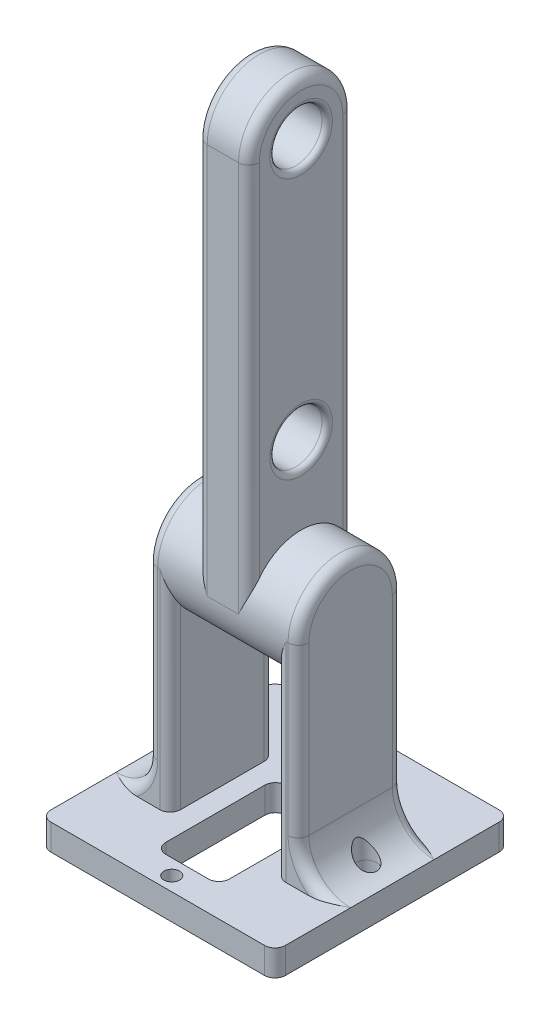
SolidWorks part; units mm, degrees
other "Base"
other "Brazo"
ref_plane "Alzado" through (0, 0, 0) normal (0, 0, 1) x (1, 0, 0)
ref_plane "Planta" through (0, 0, 0) normal (0, 1, 0) x (1, 0, 0)
ref_plane "Vista lateral" through (0, 0, 0) normal (1, 0, 0) x (0, 0, -1)
sketch "Croquis1" plane through (0, 0, 0) normal (0, 1, 0) x (1, 0, 0)
  line L0 (-17.5, 5.35) -> (17.5, 5.35) construction
  line L1 (-6.1, -11.5) -> (6.1, -11.5)
  line L2 (-6.1, -11.5) -> (-6.1, 11.5)
  line L3 (-6.1, 11.5) -> (6.1, 11.5)
  line L4 (6.1, -11.5) -> (6.1, 11.5)
  line L5 (-6.1, -11.5) -> (6.1, 11.5) construction
  line L6 (-6.1, 11.5) -> (6.1, -11.5) construction
  line L11 (0, 14.45) -> (0, -14.45) construction
  line L13 (-17.5, 7.35) -> (-6.1, 7.35) construction
  line L18 (-6.1, 11.5) -> (6.1, 11.5) construction
  line L22 (-22.5, -17.15) -> (22.5, -17.15)
  line L23 (-22.5, -17.15) -> (-22.5, 27.85)
  line L24 (-22.5, 27.85) -> (22.5, 27.85)
  line L25 (22.5, -17.15) -> (22.5, 27.85)
  line L26 (-22.5, -17.15) -> (22.5, 27.85) construction
  line L27 (-22.5, 27.85) -> (22.5, -17.15) construction
  line L30 (-6.1, -11.5) -> (6.1, -11.5) construction
  circle A0 centre (-17.5, 5.35) radius 2
  circle A1 centre (17.5, 5.35) radius 2
  circle A12 centre (0, 14.45) radius 1.5
  circle A13 centre (0, -14.45) radius 1.5
  point P0 (0, 0)
  point P14 (0, 5.35)
  point P17 (0, 0)
  point P41 (0, 5.35)
  dimension "D4" = 4
  dimension "D5" = 45
  dimension "D6" = 45
  dimension "D7" = 4
  dimension "D12" = 3
  dimension "D13" = 3
  dimension "D1" = 12.2
  dimension "D2" = 23
  dimension "D3" = 9.1
  dimension "D8" = 35
  dimension "D9" = 28.9
extrude "Saliente-Extruir1" add sketch "Croquis1" against normal blind 5 contours L25 L24 L23 A1 A0 L4 L1 L2 L3 region at (-21.8636, 0, -5.35)
sketch "Croquis2" plane through (0, -5, 0) normal (0, -1, 0) x (1, 0, 0)
  line L4 (-22.5, -27.85) -> (22.5, -27.85)
  line L5 (22.5, 17.15) -> (-22.5, 17.15)
  line L6 (22.5, 17.15) -> (-22.5, 17.15)
  line L7 (-22.5, 17.15) -> (-22.5, -27.85)
  line L8 (-22.5, -27.85) -> (22.5, -27.85)
  line L12 (-22.5, 17.15) -> (-22.5, -27.85)
  line L13 (22.5, -27.85) -> (22.5, 17.15)
  line L14 (22.5, -27.85) -> (22.5, 17.15)
  circle A0 centre (0, -14.45) radius 1.5 construction
  circle A1 centre (0, -14.45) radius 1.5
  circle A2 centre (0, 14.45) radius 1.5 construction
  circle A3 centre (0, 14.45) radius 1.5
  circle A12 centre (0, 14.45) radius 2
  circle A13 centre (0, -14.45) radius 2
  circle M17 centre (0, 14.45) radius 1.5
  circle M18 centre (0, -14.45) radius 1.5
  dimension "D2" = 0.5
  dimension "D3" = 0.5
  dimension "D1" = 0
extrude "Cortar-Extruir1" cut sketch "Croquis2" against normal blind 2 contours A13 M18 | A12 M17 region at (-1.9434, -5, 14.45) region at (-1.9434, -5, -14.45)
sketch "Croquis3" plane through (0, 0, 0) normal (1, 0, 0) x (0, 0, -1)
  line L1 (-17.15, 0) -> (27.85, 0) construction
  line L3 (5.35, 0) -> (5.35, 125) construction
  line L4 (-4.65, 115) -> (-4.65, 40)
  line L6 (15.35, 115) -> (15.35, 40)
  circle A1 centre (5.35, 40) radius 10
  circle A3 centre (5.35, 65) radius 5
  circle A4 centre (5.35, 115) radius 5
  circle A5 centre (5.35, 115) radius 10
  point P2 (5.35, 60)
  point P3 (5.35, 50)
  point P6 (5.35, 30)
  point P20 (5.35, 120)
  dimension "D1" = 50
  dimension "D3" = 30
  dimension "D5" = 10
  dimension "D6" = 10
  dimension "D7" = 5
  dimension "D2" = 10
extrude "Saliente-Extruir2" add sketch "Croquis3" along normal mid plane 10 separate body contours A1 L3 A3 A5 L4 | L3 A1 L6 A5 A3 | L3 A5 A4 | A5 L3 A4 | A1 region at (0, 78.3866, 0.0686) region at (0, 78.3866, -10.7686) region at (0, 121.913, 1.563) region at (0, 108.087, -12.263)
sketch "Croquis4" plane through (0, 0, 0) normal (0, 1, 0) x (1, 0, 0)
  line L5 (22.5, -17.15) -> (22.5, 27.85) construction
  line L6 (12.5, -4.65) -> (22.5, -4.65)
  line L7 (12.5, -4.65) -> (12.5, 15.35)
  line L8 (12.5, 15.35) -> (22.5, 15.35)
  line L9 (22.5, -4.65) -> (22.5, 15.35)
  line L10 (12.5, -4.65) -> (22.5, 15.35) construction
  line L11 (12.5, 15.35) -> (22.5, -4.65) construction
  line L12 (12.5, 15.35) -> (10.1, 15.35)
  line L13 (10.1, 15.35) -> (10.1, -4.65)
  line L14 (10.1, -4.65) -> (12.5, -4.65)
  line L15 (6.1, -11.5) -> (6.1, 11.5) construction
  line L16 (14.5, 15.35) -> (14.5, -4.65) construction
  circle A0 centre (17.5, 5.35) radius 2 construction
  circle A1 centre (17.5, 5.35) radius 2
  point P15 (15.5, 5.35)
  dimension "D1" = 10
  dimension "D2" = 20
  dimension "D3" = 4
  dimension "D4" = 1
  dimension "D5" = 4.4
ref_plane "Plano1" through (0, 0, 4.65) normal (0, 0, 1) x (1, 0, 0)
sketch "Croquis5" plane through (0, 0, 4.65) normal (0, 0, 1) x (1, 0, 0)
  line L0 (10.1, 0) -> (10.1, 40)
  line L1 (5, 40) -> (-5, 40) construction
  line L2 (14.5, 0) -> (14.5, 8) construction
  line L3 (12.5, 0) -> (22.5, 0) construction
  line L4 (14.5, 8) -> (14.5, 40)
  line L5 (14.5, 40) -> (10.1, 40)
  line L6 (10.1, 0) -> (22.5, 0)
  arc A0 (22.5, 0) -> (14.5, 8) centre (22.5, 8) cw
  point P1 (22.5, 0)
extrude "Saliente-Extruir4" add sketch "Croquis5" against normal up to vertex (20 mm away) separate body contours L6 L2 L4 L5 L0 | L2 L6 A0 region at (12.3, 20, 4.65) region at (16.2869, 1.7869, 4.65) up to point (22.5, 0, -15.35)
extrude "Cortar-Extruir2" cut sketch "Croquis4" along normal blind 10 contours A1
sketch "Croquis6" plane through (14.5, 0, 0) normal (1, 0, 0) x (0, 0, -1)
  circle A0 centre (5.35, 40) radius 10
extrude "Saliente-Extruir5" add sketch "Croquis6" against normal up to surface (9.5 mm away) up to face at (5, 77.5, -5.35)
fillet "Redondeo3" radius 2 8 edges at (-22.5, -2.5, -27.85) (6.1, -2.5, 11.5) (6.1, -2.5, -11.5) (-6.1, -2.5, 11.5) (-6.1, -2.5, -11.5) (-22.5, -2.5, 17.15) (22.5, -2.5, 17.15) (22.5, -2.5, -27.85)
fillet "Redondeo4" radius 1 4 edges at (-5, 65, -10.35) (5, 65, -10.35) (-5, 115, -10.35) (5, 115, -10.35)
mirror "Simetría3" about plane through (0, 0, 0) normal (1, 0, 0) of bodies 119
combine bodies "Combinar2" operation type add bodies to combine 115 122 119
fillet "Redondeo5" radius 2 20 edges at (-5, 77.5, 4.65) (-5, 125, -5.35) (5, 77.5, 4.65) (5, 125, -5.35) (16.8431, 2.3431, 4.65) (16.8431, 2.3431, -15.35) (14.5, 24, -15.35) (14.5, 50, -5.35) (-16.8431, 2.3431, 4.65) (-16.8431, 2.3431, -15.35) (-14.5, 24, -15.35) (-14.5, 50, -5.35) (-5, 77.5, -15.35) (5, 77.5, -15.35) (-10.1, 20, -15.35) (10.1, 20, -15.35) (14.5, 24, 4.65) (10.1, 20, 4.65) (-10.1, 20, 4.65) (-14.5, 24, 4.65)
